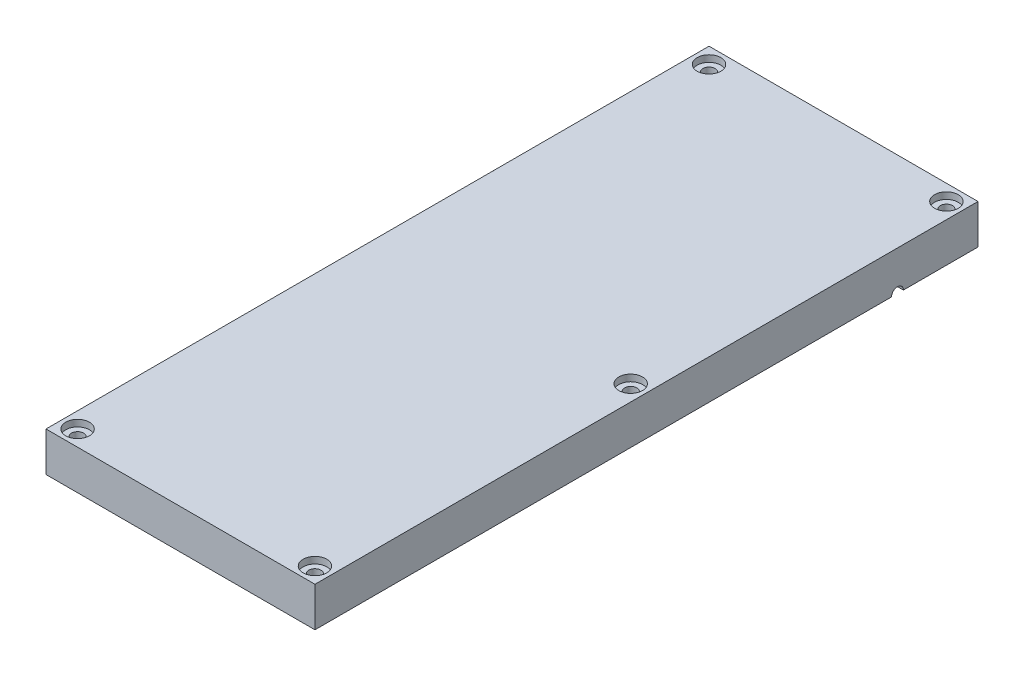
SolidWorks part; units mm, degrees
ref_plane "Front Plane" through (0, 0, 0) normal (0, 0, 1) x (1, 0, 0)
ref_plane "Top Plane" through (0, 0, 0) normal (0, 1, 0) x (1, 0, 0)
ref_plane "Right Plane" through (0, 0, 0) normal (1, 0, 0) x (0, 0, -1)
sketch "Sketch1" plane through (0, 0, 0) normal (0, 1, 0) x (1, 0, 0)
  line L1 (37.8587, 0) -> (146.05, 0)
  line L2 (37.8587, 0) -> (37.8587, 266.7)
  line L3 (37.8587, 266.7) -> (146.05, 266.7)
  line L4 (146.05, 0) -> (146.05, 266.7)
  dimension "D1" = 266.7
  dimension "D2" = 108.1913
  dimension "D3" = 146.05
  dimension "D4" = 266.7
extrude "Boss-Extrude1" add sketch "Sketch1" along normal blind 15.875 from offset 15.875
hole_wizard "CBORE for #8 Binding Head Machine Screw1" positions "Sketch3" profile "Sketch2" counterbore size "#8" standard "ANSI Inch" end condition through all
sketch "Sketch3" plane through (0, 31.75, 0) normal (0, 1, 0) x (1, 0, 0)
  line L0 (146.05, 0) -> (146.05, 266.7) construction
  line L1 (37.8587, 0) -> (146.05, 0) construction
  line L2 (146.05, 266.7) -> (37.8587, 266.7) construction
  line L3 (37.8587, 266.7) -> (37.8587, 0) construction
  point P0 (139.7, 6.35)
  point P2 (139.7, 260.35)
  point P13 (44.2087, 6.35)
  point P15 (44.2087, 260.35)
  point P20 (139.7, 133.35)
  dimension "D1" = 6.35
  dimension "D2" = 6.35
  dimension "D3" = 6.35
  dimension "D4" = 6.35
  dimension "D5" = 6.35
  dimension "D6" = 6.35
  dimension "D7" = 6.35
  dimension "D8" = 6.35
  dimension "D9" = 6.35
  dimension "D10" = 133.35
  dimension "D11" = 133.35
sketch "Sketch2" plane through (139.7, 31.75, -6.35) normal (1, 0, 0) x (0, 0, 1)
  line L0 (0, 0) -> (0, 15.875)
  line L1 (0, 15.875) -> (2.4574, 15.875)
  line L3 (2.4574, 15.875) -> (2.4575, 2.667)
  line L4 (2.4575, 2.667) -> (4.7625, 2.667)
  line L5 (4.7625, 2.667) -> (4.7625, 0)
  line L7 (4.7625, 0) -> (0, 0)
  line L11 (0, -6.35) -> (0, 107.95) construction
  dimension "Thru Hole Dia." = 4.9149
  dimension "Thru Hole Depth" = 15.875
  dimension "C'Bore Dia." = 9.525
  dimension "C'Bore Depth" = 2.667
sketch "Sketch4" plane through (0, 15.875, 0) normal (0, -1, 0) x (-1, 0, 0)
  line L0 (-37.8587, 266.7) -> (-37.8587, 0) construction
  line L1 (-44.2087, 18.415) -> (-116.205, 18.415)
  line L2 (-44.2087, 18.415) -> (-44.2087, 243.205)
  line L3 (-44.2087, 243.205) -> (-116.205, 243.205)
  line L4 (-116.205, 18.415) -> (-116.205, 243.205)
  line L5 (-37.8587, 0) -> (-146.05, 0) construction
  dimension "D1" = 6.35
  dimension "D2" = 18.415
  dimension "D3" = 224.79
  dimension "D4" = 71.9963
extrude "Cut-Extrude1" cut sketch "Sketch4" against normal blind 12.7
sketch "Sketch5" plane through (0, 15.875, 0) normal (0, -1, 0) x (1, 0, 0)
  line L0 (116.205, -196.215) -> (121.92, -196.215)
  line L1 (116.205, -243.205) -> (116.205, -18.415) construction
  line L2 (121.92, -196.215) -> (121.92, -234.315)
  line L3 (121.92, -234.315) -> (130.81, -234.315)
  line L4 (130.81, -234.315) -> (130.81, -158.115)
  line L5 (130.81, -158.115) -> (139.7, -158.115)
  line L6 (139.7, -158.115) -> (139.7, -234.315)
  line L7 (139.7, -234.315) -> (146.05, -234.315)
  line L8 (146.05, 0) -> (146.05, -266.7) construction
  line L9 (116.205, -18.415) -> (44.2087, -18.415) construction
  dimension "D1" = 38.1
  dimension "D2" = 76.2
  dimension "D3" = 76.2
  dimension "D4" = 5.715
  dimension "D5" = 8.89
  dimension "D6" = 8.89
  dimension "D7" = 177.8
  dimension "D8" = 6.35
sketch "Sketch6" plane through (146.05, 0, 0) normal (1, 0, 0) x (0, 0, -1)
  line L0 (234.315, 15.875) -> (158.115, 15.875) construction
  line L1 (196.215, 15.875) -> (234.315, 15.875) construction
  circle A0 centre (234.315, 15.875) radius 2.3813
  dimension "D1" = 4.7625
  dimension "D2" = 0
sweep "Cut-Sweep1" cut profiles "Sketch6" path "Sketch5"
sketch "Sketch8" plane through (0, 15.875, 0) normal (0, -1, 0) x (1, 0, 0)
  line L0 (116.205, -193.8337) -> (116.205, -18.415) construction
  line L1 (116.205, -18.415) -> (128.905, -18.415)
  line L2 (116.205, -18.415) -> (116.205, -32.385)
  line L3 (116.205, -32.385) -> (128.905, -32.385)
  line L4 (128.905, -18.415) -> (128.905, -32.385)
  line L5 (44.2087, -243.205) -> (116.205, -243.205) construction
  line L6 (102.235, -243.205) -> (116.205, -243.205)
  line L7 (102.235, -243.205) -> (102.235, -255.905)
  line L8 (102.235, -255.905) -> (116.205, -255.905)
  line L9 (116.205, -243.205) -> (116.205, -255.905)
  line L10 (116.205, -243.205) -> (116.205, -18.415) construction
  line L11 (116.205, -18.415) -> (44.2087, -18.415) construction
  dimension "D1" = 12.7
  dimension "D2" = 13.97
  dimension "D3" = 12.7
  dimension "D4" = 13.97
  dimension "D5" = 0
  dimension "D6" = 0
extrude "Cut-Extrude3" cut sketch "Sketch8" against normal blind 12.7
